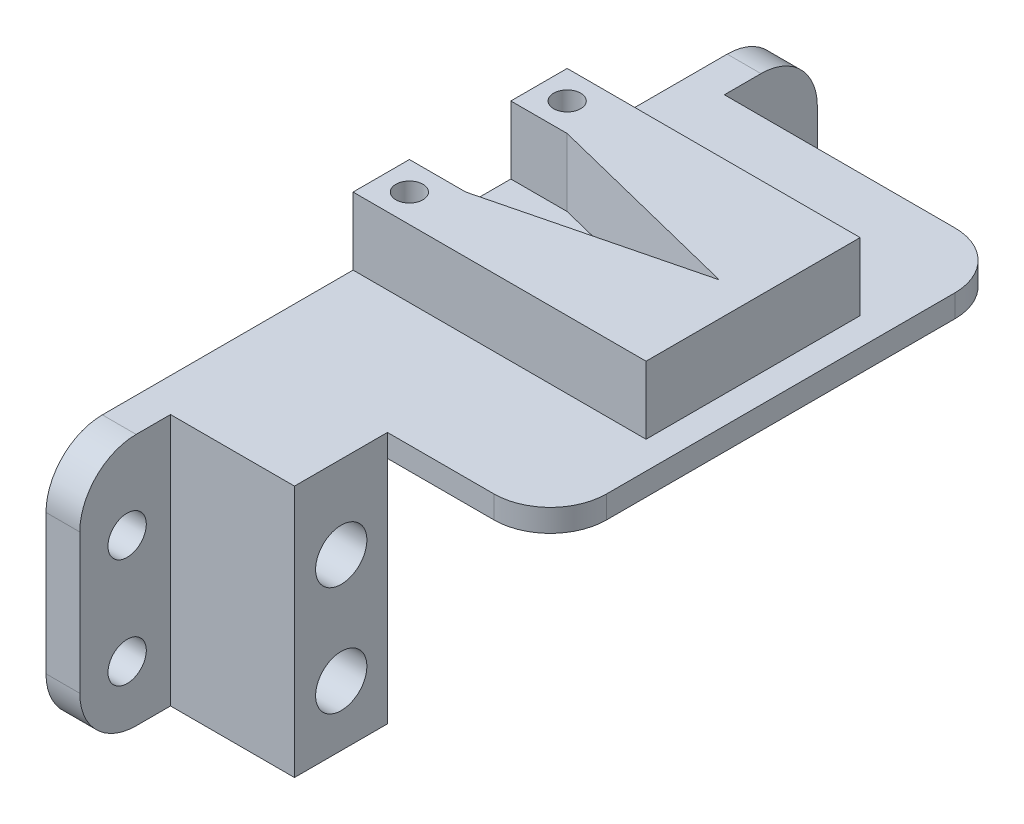
SolidWorks part; units mm, degrees
ref_plane "Front Plane" through (0, 0, 0) normal (0, 0, 1) x (1, 0, 0)
ref_plane "Top Plane" through (0, 0, 0) normal (0, 1, 0) x (1, 0, 0)
ref_plane "Right Plane" through (0, 0, 0) normal (1, 0, 0) x (0, 0, -1)
sketch "Sketch1" plane through (0, 0, 0) normal (0, 1, 0) x (1, 0, 0)
  line L0 (22.375, 20.45) -> (-6.075, 20.45)
  line L1 (-22.375, 28.7) -> (22.375, 28.7)
  line L2 (-22.375, 28.7) -> (-22.375, -28.7)
  line L3 (-22.375, -28.7) -> (22.375, -28.7)
  line L4 (22.375, 28.7) -> (22.375, -28.7)
  line L5 (-22.375, 28.7) -> (22.375, -28.7) construction
  line L6 (-22.375, -28.7) -> (22.375, 28.7) construction
  line L7 (-6.075, 20.45) -> (-6.075, 28.7)
  line L8 (22.375, -20.45) -> (-6.075, -20.45)
  line L9 (-6.075, -20.45) -> (-6.075, -28.7)
  line L10 (-6.075, -20.45) -> (-6.075, 20.45)
  line L11 (7.925, -20.45) -> (7.925, -28.7)
  line L12 (22.375, -28.7) -> (24.375, -28.7)
  line L13 (22.375, -28.7) -> (22.375, 28.7)
  line L14 (22.375, 28.7) -> (24.375, 28.7)
  line L15 (24.375, -28.7) -> (24.375, 28.7)
  line L16 (22.375, -20.45) -> (24.375, -20.45)
  line L17 (7.925, 28.7) -> (7.925, 20.45)
  line L18 (-3.075, 28.7) -> (-3.075, 20.45)
  point P0 (0, 0)
  point P11 (-6.075, 0)
  dimension "D1" = 28.45
  dimension "D2" = 16.3
  dimension "D3" = 40.9
  dimension "D4" = 57.4
  dimension "D5" = 2
  dimension "D6" = 14
  dimension "D7" = 3
extrude "Boss-Extrude1" add sketch "Sketch1" along normal blind 2 contours L10 L8 L4 L0 | L11 L8 L9 L3 | L18 L1 L7 L0 region at (8.15, 0, 0) region at (-4.575, 0, -24.575) region at (0.925, 0, 24.575)
extrude "Boss-Extrude2" add sketch "Sketch1<3>" against normal blind 20.4 contours L11 L8 L9 L3 | L18 L1 L7 L0 region at (-4.575, 0, -24.575) region at (0.925, 0, 24.575)
sketch "Sketch1<3>" plane through (0, 0, 0) normal (0, 1, 0) x (1, 0, 0) same geometry as "Sketch1"
sketch "Sketch5" plane through (0, 0, 0) normal (1, 0, 0) x (0, 0, -1)
  line L1 (-28.7, 2) -> (-36.75, 2)
  line L2 (-28.7, 2) -> (-28.7, -20.4)
  line L3 (-28.7, -20.4) -> (-36.75, -20.4)
  line L4 (-36.75, 2) -> (-36.75, -20.4)
  line L5 (-28.7, 2) -> (-28.7, -20.4) construction
  line L6 (-20.45, -20.4) -> (-28.7, -20.4) construction
  line L7 (-28.7, 2) -> (28.7, 2) construction
  dimension "D1" = 8.05
extrude "Boss-Extrude4" add sketch "Sketch5" along normal blind 3 from surface starting at face at (-6.075, -9.7, 0)
sketch "Sketch2" plane through (0, 0, 0) normal (1, 0, 0) x (0, 0, -1)
  line L0 (24.55, -5.35) -> (24.55, -15.05) construction
  line L1 (-24.55, -5.35) -> (-24.55, -15.05) construction
  line L2 (-24.55, -10.2) -> (24.55, -10.2) construction
  line L3 (-28.7, 0) -> (28.7, 0) construction
  circle A0 centre (24.55, -15.05) radius 1.7
  circle A1 centre (-24.55, -15.05) radius 2.275
  circle A2 centre (-24.55, -5.35) radius 2.275
  circle A3 centre (24.55, -5.35) radius 1.7
  circle A4 centre (-32.55, -5.35) radius 1.7
  circle A5 centre (-32.55, -15.05) radius 1.7
  point P10 (24.55, -10.2)
  point P13 (0, -10.2)
  point P19 (0, 0)
  point P20 (0, 0)
  point P21 (0, 0)
  dimension "D4" = 4.55
  dimension "D5" = 4.55
  dimension "D6" = 3.4
  dimension "D7" = 3.4
  dimension "D9" = 3.4
  dimension "D10" = 3.4
  dimension "D1" = 9.7
  dimension "D2" = 49.1
  dimension "D3" = 10.2
  dimension "D8" = 8
extrude "Cut-Extrude1" cut sketch "Sketch2" along normal through all from surface starting at face at (-6.075, -9.7, 2.0125)
sketch "Sketch3" plane through (0, 0, 0) normal (0, 1, 0) x (1, 0, 0)
  line L0 (-3.575, 7) -> (-3.575, -7) construction
  line L1 (-6.075, -20.45) -> (-6.075, 20.45) construction
  line L2 (-6.075, 9.5) -> (-1.075, 9.5)
  line L3 (-6.075, 9.5) -> (-6.075, 4.5)
  line L4 (-6.075, 4.5) -> (-1.075, 4.5)
  line L5 (-1.075, 9.5) -> (-1.075, 4.5)
  line L6 (-6.075, 9.5) -> (-1.075, 4.5) construction
  line L7 (-6.075, 4.5) -> (-1.075, 9.5) construction
  line L8 (-6.075, -9.5) -> (-1.075, -9.5)
  line L9 (-6.075, -9.5) -> (-6.075, -4.5)
  line L10 (-6.075, -4.5) -> (-1.075, -4.5)
  line L11 (-1.075, -9.5) -> (-1.075, -4.5)
  line L12 (-6.075, -9.5) -> (-1.075, -4.5) construction
  line L13 (-6.075, -4.5) -> (-1.075, -9.5) construction
  line L14 (19.925, 9.5) -> (16.925, 9.5)
  line L15 (19.925, 9.5) -> (19.925, -9.5)
  line L16 (19.925, -9.5) -> (16.925, -9.5)
  line L17 (16.925, 9.5) -> (16.925, -9.5)
  line L18 (19.925, 9.5) -> (16.925, -9.5) construction
  line L19 (19.925, -9.5) -> (16.925, 9.5) construction
  line L20 (-1.075, 9.5) -> (16.925, 9.5)
  line L21 (-1.075, 4.5) -> (16.925, 0)
  line L22 (-1.075, -9.5) -> (16.925, -9.5)
  line L23 (-1.075, -4.5) -> (16.925, 0)
  circle A0 centre (-3.575, 7) radius 1.2
  circle A1 centre (-3.575, -7) radius 1.2
  point P4 (-3.575, 0)
  point P14 (18.425, 0)
  dimension "D2" = 2.4
  dimension "D3" = 2.4
  dimension "D1" = 14
  dimension "D4" = 5
  dimension "D5" = 5
  dimension "D7" = 5
  dimension "D8" = 3
  dimension "D9" = 22
extrude "Boss-Extrude3" add sketch "Sketch3" along normal blind 8 contours L5 L2 L3 L4 A0 | L8 L11 L10 L9 A1 | L5 L21 L17 L20 | L23 L11 L22 L17 | L14 L17 L16 L15 region at (-3.575, 0, -9.4293) region at (8.856, 0, -5.7586) region at (18.425, 0, 0) region at (8.856, 0, 5.7586) region at (-1.1457, 0, 7)
fillet "Fillet1" radius 5 6 edges at (-4.575, -20.4, 36.75) (-4.575, 2, -28.7) (-4.575, 2, 36.75) (22.375, 1, -20.45) (22.375, 1, 20.45) (-4.575, -20.4, -28.7)
